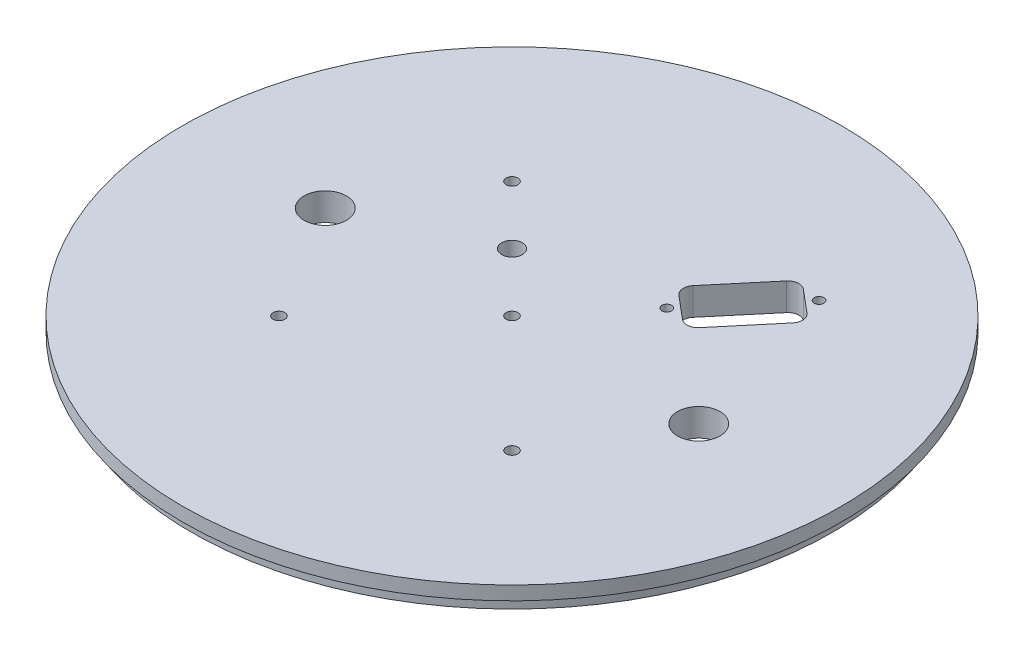
SolidWorks part; units mm, degrees
material "6061-T6 (SS)"
ref_plane "Front Plane" through (0, 0, 0) normal (0, 0, 1) x (1, 0, 0)
ref_plane "Top Plane" through (0, 0, 0) normal (0, 1, 0) x (1, 0, 0)
ref_plane "Right Plane" through (0, 0, 0) normal (1, 0, 0) x (0, 0, -1)
sketch "Sketch1" plane through (0, 0, 0) normal (0, 1, 0) x (1, 0, 0)
  line L0 (0, -76.2) -> (0, 76.2) construction
  line L1 (-76.2, 0) -> (76.2, 0) construction
  line L2 (-26.9408, 26.9408) -> (0, 0) construction
  line L3 (0, 56.7387) -> (0, 29.6936) construction
  line L4 (3.6407, 56.7387) -> (3.6407, 29.6936) construction
  line L5 (-3.6407, 56.7387) -> (-3.6407, 29.6936) construction
  line L6 (0, -56.7387) -> (0, -29.6936) construction
  line L7 (3.6407, -56.7387) -> (3.6407, -29.6936) construction
  line L8 (-3.6407, -56.7387) -> (-3.6407, -29.6936) construction
  line L9 (-53.8815, -53.8815) -> (54.3236, 54.3236) construction
  line L10 (-26.9408, -26.9408) -> (0, 0) construction
  circle A0 centre (0, 0) radius 76.2
  circle A1 centre (0, 0) radius 3.175 construction
  circle A2 centre (43.18, 0) radius 4.9022
  circle A3 centre (-43.18, 0) radius 4.9022
  circle A4 centre (-26.9408, 26.9408) radius 1.3589
  arc A6 (3.6407, 56.7387) -> (-3.6407, 56.7387) centre (0, 56.7387) ccw construction
  arc A7 (-3.6407, 29.6936) -> (3.6407, 29.6936) centre (0, 29.6936) ccw construction
  arc A8 (3.6407, -56.7387) -> (-3.6407, -56.7387) centre (0, -56.7387) cw construction
  arc A9 (-3.6407, -29.6936) -> (3.6407, -29.6936) centre (0, -29.6936) cw construction
  circle A10 centre (26.9408, -26.9408) radius 1.3589
  circle A11 centre (-13.4704, 13.4704) radius 2.3813
  circle A13 centre (-26.9408, -26.9408) radius 1.3589
  circle A14 centre (0, 0) radius 38.1 construction
  circle A15 centre (0, 0) radius 1.3589
  point P16 (0, 43.2162)
  point P19 (0, 0)
  point P26 (0, -43.2162)
  dimension "D1" = 152.4
  dimension "D2" = 6.35
  dimension "D3" = 9.8044
  dimension "D5" = 2.7178
  dimension "D8" = 4.7625
  dimension "D10" = 2.7178
  dimension "D12" = 2.7178
  dimension "D6" = 38.1
  dimension "D7" = 45
  dimension "D4" = 45
  dimension "D9" = 43.18
  dimension "D11" = 38.1
extrude "Boss-Extrude1" add sketch "Sketch1" along normal blind 6.35
sketch "Sketch2" plane through (0, 0, 0) normal (0, -1, 0) x (1, 0, 0)
  circle A0 centre (0, 0) radius 76.2
  circle A1 centre (0, 0) radius 74.041
  dimension "D1" = 152.4
  dimension "D2" = 148.082
extrude "Cut-Extrude1" cut sketch "Sketch2" against normal blind 3.175
sketch "Sketch3" plane through (0, 6.35, 0) normal (0, 1, 0) x (1, 0, 0)
  line L0 (0, 76.2) -> (0, -76.2) construction
  line L1 (-76.2, 0) -> (76.2, 0) construction
  line L2 (0, 34.798) -> (0, 13.97) construction
  line L3 (3.2385, 34.798) -> (3.2385, 13.97)
  line L4 (-3.2385, 34.798) -> (-3.2385, 13.97)
  line L5 (0, -34.798) -> (0, -13.97) construction
  line L6 (3.2385, -34.798) -> (3.2385, -13.97)
  line L7 (-3.2385, -34.798) -> (-3.2385, -13.97)
  circle A0 centre (0, 0) radius 76.2 construction
  arc A1 (3.2385, 34.798) -> (-3.2385, 34.798) centre (0, 34.798) ccw
  arc A2 (-3.2385, 13.97) -> (3.2385, 13.97) centre (0, 13.97) ccw
  arc A3 (3.2385, -34.798) -> (-3.2385, -34.798) centre (0, -34.798) cw
  arc A4 (-3.2385, -13.97) -> (3.2385, -13.97) centre (0, -13.97) cw
  point P7 (0, 13.97)
  point P8 (0, 34.798)
  point P12 (0, 24.384)
  point P20 (0, -24.384)
  point P25 (0, -34.798)
  point P26 (0, -13.97)
  dimension "D1" = 13.97
  dimension "D2" = 20.828
  dimension "D3" = 6.477
extrude "Cut-Extrude2" cut sketch "Sketch3" against normal blind 3.556 from offset 3.175 offset against normal yes
hole_wizard "Tap Drill for #4-40 Tap1" positions "Sketch5" profile "Sketch6" hole size "#4-40" standard "ANSI Inch" end condition through all
sketch "Sketch5" plane through (0, 6.35, 0) normal (0, 1, 0) x (1, 0, 0)
  line L0 (0, 0) -> (53.6567, 63.9455) construction
  line L2 (0, 0) -> (43.18, 0) construction
  point P0 (16.3268, 19.4575)
  point P2 (32.3965, 38.6086)
  dimension "D1" = 50
  dimension "D2" = 25
  dimension "D3" = 25.4
sketch "Sketch6" plane through (16.3268, 6.35, -19.4575) normal (1, 0, 0) x (0, 0, 1)
  line L0 (0, 0) -> (0, 6.35)
  line L1 (0, 6.35) -> (1.1303, 6.35)
  line L2 (1.1303, 6.35) -> (1.1303, 0)
  line L5 (1.1303, 0) -> (0, 0)
  line L11 (0, -6.35) -> (0, 107.95) construction
  dimension "Thru Hole Dia." = 2.2606
  dimension "Thru Hole Depth" = 6.35
sketch "Sketch4" plane through (0, 6.35, 0) normal (0, 1, 0) x (1, 0, 0)
  line L0 (15.1695, 23.4128) -> (20.423, 19.0046)
  line L1 (14.8564, 26.9913) -> (24.7219, 38.7485)
  line L2 (24.0014, 19.3177) -> (33.8669, 31.0749)
  line L3 (28.3003, 39.0616) -> (33.5538, 34.6533)
  line L4 (0, 0) -> (32.3965, 38.6086) construction
  circle A1 centre (16.3268, 19.4575) radius 1.1303 construction
  arc A2 (24.7219, 38.7485) -> (28.3003, 39.0616) centre (26.6676, 37.1158) cw
  arc A3 (33.8669, 31.0749) -> (33.5538, 34.6533) centre (31.9212, 32.7076) ccw
  arc A4 (20.423, 19.0046) -> (24.0014, 19.3177) centre (22.0557, 20.9503) ccw
  arc A5 (14.8564, 26.9913) -> (15.1695, 23.4128) centre (16.8021, 25.3586) ccw
  point P11 (17.7962, 21.2087)
  dimension "D4" = 2.54
  dimension "D1" = 2.286
  dimension "D2" = 2.286
  dimension "D3" = 11.938
extrude "Cut-Extrude3" cut sketch "Sketch4" against normal through all
equation "\"leadDist\"=1.5"
equation "\"Lead_Screw_Dist\" = 3.4in"
equation "\"D9@Sketch1\"=\"Lead_Screw_Dist\"/2"
equation "\"Lead_Screw_Diam\" = 0.386in"
equation "\"D3@Sketch1\"=\"Lead_Screw_Diam\""
equation "\"Bodytube_OD\" = 6.17in"
equation "\"Bodytube_ID\" = 5.998in"
equation "\"Motor_OD\" = 4in"
equation "\"Fwd_Tube_Length\" = 40in"
equation "\"Mid_Tube_Length\" = 1in"
equation "\"Aft_Section_Length\"= 39in"
equation "\"AB_Coupler_OD_Length\"= 1in"
equation "\"AB_Coupling_Section_Length\"= 0.375in"
equation "\"AB_Coupler_Length\"= \"AB_Coupler_OD_Length\" + \"AB_Coupling_Section_Length\" * 2"
equation "\"Cutout_Angle\" = 80"
equation "\"AB_Paddle_Height\" = 0.375in"
equation "\"AB_Coupler_Num_Screws\"= 4"
equation "\"Num_Cutouts\" = 3"
equation "\"AB_Coupler_OD\"= 6.17in"
equation "\"AB_Coupler_ID\"= 5.75in"
equation "\"AB_Coupler_Surface_Diameter\"= 5.998in"
equation "\"AB_Coupling_Screw_Diameter\"= 0.15748in"
equation "\"AB_Central_Bushing_Length\" = .4724in"
equation "\"Lead_Screw_Length\" = (\"Mid_Coupler_Length\" + 2*0.375in + 2*0.5in)"
equation "\"Paddle_Pin_Offset\" = .25in"
equation "\"Paddle_Pin_Radius\" = 2.25in"
equation "\"SS_Paddle_Pin_Radius\" = 2.25*0.66in"
equation "\"Paddle_Gear_OD\" = 3.2in"
equation "\"Drive_Gear_OD\" = 1.7in"
equation "\"Fwd_BKHD_From_Top\" = 18in"
equation "\"Fin_Thickness\"= .118in"
equation "\"Guiderail_Cutout_Diameter\"= 1.5in"
equation "\"DB9_Hole_Dist\" = 25mm"
equation "\"Airbrakes_Wire_Hole_Dia\" = .25in"
equation "\"Airbrakes_Wire_Hole_Dist\" = 1.1in"
equation "\"Servo_Gear_Offset\" = 0.5in"
equation "\"Mid_Coupler_Length\" = 13in"
equation "\"D2@Sketch5\"=\"DB9_Hole_Dist\""
equation "\"DB9_Relief_Width\" = 0.47in"
equation "\"DB9_Relief_Hole_Offset\" = 0.09in"
equation "\"D1@Sketch4\"=\"DB9_Relief_Hole_Offset\""
equation "\"D2@Sketch4\"=\"DB9_Relief_Hole_Offset\""
equation "\"D3@Sketch4\"=\"DB9_Relief_Width\""
